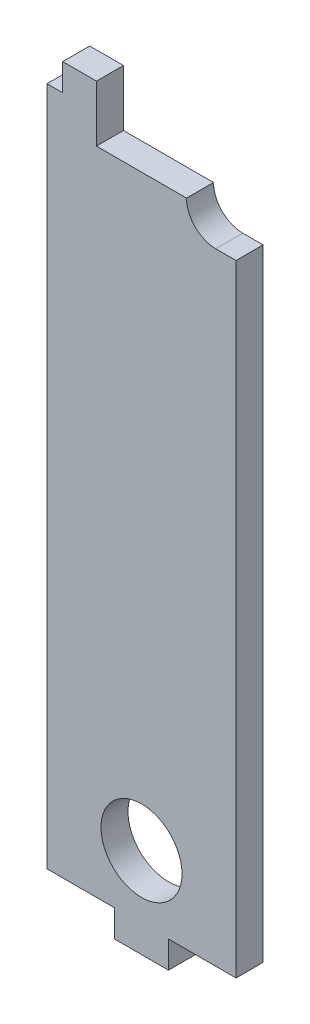
SolidWorks part; units mm, degrees
ref_plane "Front Plane" through (0, 0, 0) normal (0, 0, 1) x (1, 0, 0)
ref_plane "Top Plane" through (0, 0, 0) normal (0, 1, 0) x (1, 0, 0)
ref_plane "Right Plane" through (0, 0, 0) normal (1, 0, 0) x (0, 0, -1)
sketch "Sketch2" plane through (0, 0, 0) normal (0, 1, 0) x (1, 0, 0)
  line L0 (0, 0) -> (0, 6) construction
sketch "Sketch1" plane through (0, 0, 0) normal (0, 0, 1) x (1, 0, 0)
  line L0 (10, 75.5) -> (10, 69)
  line L1 (-21, -75.5) -> (21, -75.5)
  line L2 (-21, -75.5) -> (-21, 75.5)
  line L3 (-21, 75.5) -> (21, 75.5)
  line L4 (21, -75.5) -> (21, 75.5)
  line L5 (-21, -75.5) -> (21, 75.5) construction
  line L6 (-21, 75.5) -> (21, -75.5) construction
  line L7 (10, 69) -> (-10, 69)
  line L8 (-10, 69) -> (-10, 75.5)
  line L9 (0, 69) -> (0, 75.5) construction
  line L10 (16.5, 62.5) -> (21, 62.5)
  line L11 (-17.5, 75.5) -> (-23.5, 75.5)
  line L12 (-21, -75.5) -> (-23.5, -75.5) construction
  line L13 (-23.5, -75.5) -> (-23.5, 75.5) construction
  line L14 (-23.5, 75.5) -> (-21, 75.5) construction
  line L15 (-17.5, 75.5) -> (-17.5, 81.5)
  line L16 (-17.5, 81.5) -> (-10, 81.5)
  line L17 (-10, 81.5) -> (-10, 75.5)
  line L18 (0, -75.5) -> (0, -61.5) construction
  line L19 (-6, -75.5) -> (-6, -81.5)
  line L20 (-6, -81.5) -> (6, -81.5)
  line L21 (6, -81.5) -> (6, -75.5)
  line L22 (0, -81.5) -> (0, -75.5)
  line L23 (16.5, 69) -> (16.5, 62.5) construction
  line L24 (16.5, 69) -> (10, 69) construction
  circle A0 centre (0, -61.5) radius 9
  arc A1 (10, 69) -> (16.5, 62.5) centre (16.5, 69) ccw
  point P0 (0, 0)
  point P13 (-17.5, 75.5)
  dimension "D9" = 18
  dimension "D1" = 151
  dimension "D2" = 42
  dimension "D3" = 6.5
  dimension "D4" = 20
  dimension "D6" = 2.5
  dimension "D7" = 6
  dimension "D8" = 6
  dimension "D10" = 12
  dimension "D11" = 20
extrude "Boss-Extrude1" add sketch "Sketch1" against normal up to vertex (6 mm away) contours L7 L8 L3 L2 L1 L4 A0 | L22 L20 L21 L1 | L20 L22 L1 L19 | L17 L16 L15 L3 region at (-0.3628, -0.5203, 0) region at (-13.75, 78.5, 0) region at (3, -78.5, 0) region at (-3, -78.5, 0) up to point (0, 0, -6)
equation "\"t_wood\"= 6' Thickness of the wood"
equation "\"t_glass\"= 2.5'Thickness of glass panels"
equation "\"w_glass\"= 181"
equation "\"h_glass\"= 151"
equation "\"h_food_internal\" = 60"
equation "\"entry_height\"= 20"
equation "\"entry diameter\"= 8"
equation "\"glass_bottom_overlap\"= 8"
equation "\"default_finger_size\"= 12"
equation "\"brood_depth\"= 42"
equation "\"outer_box_depth\" = \"brood_depth\" + ( 2 * \"t_glass\" ) + ( 2 * \"t_wood\" )"
equation "\"outer_box_width\"= \"w_glass\" + ( 2 * \"t_wood\" )"
equation "\"food_top_clearance\"= 10"
equation "\"outer_box_height\"= \"t_wood\" + \"h_glass\" + \"t_wood\" + \"h_food_internal\" + \"food_top_clearance\" + \"t_wood\""
equation "\"food_internal_depth\"= \"brood_depth\" + \"t_glass\" + \"t_glass\" - \"t_wood\" - \"t_wood\""
equation "\"food_channel_clearance_width\"= 14"
equation "\"bar_top_play\"= 0.5"
equation "\"bar_entry_angle\"= 10"
equation "\"bar_width\"= 20"
equation "\"entry_disk_play\"= 0.3"
equation "\"D1@Sketch2\"=\"t_wood\""
equation "\"D1@Sketch1\"=\"h_glass\""
equation "\"D2@Sketch1\"=\"brood_depth\""
equation "\"D3@Sketch1\"=\"bar_top_play\"+\"t_wood\""
equation "\"D4@Sketch1\"=\"bar_width\""
equation "\"D6@Sketch1\"=\"t_glass\""
equation "\"D7@Sketch1\"=\"t_wood\""
equation "\"D9@Sketch1\"=\"entry diameter\" +10"
equation "\"D8@Sketch1\"=\"t_wood\""
equation "\"D10@Sketch1\"=\"default_finger_size\""
equation "\"D11@Sketch1\"=\"entry_height\""
